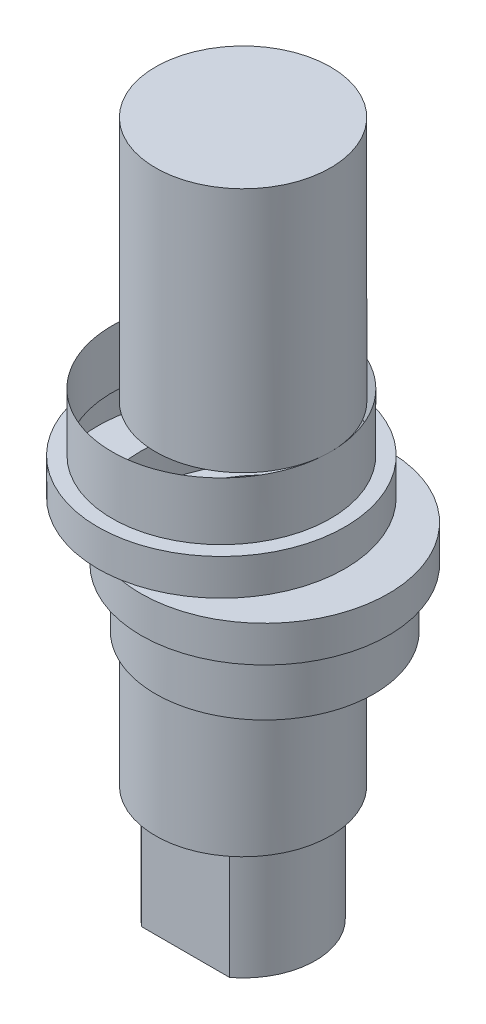
SolidWorks part; units mm, degrees
ref_plane "Front Plane" through (0, 0, 0) normal (0, 0, 1) x (1, 0, 0)
ref_plane "Top Plane" through (0, 0, 0) normal (0, 1, 0) x (1, 0, 0)
ref_plane "Right Plane" through (0, 0, 0) normal (1, 0, 0) x (0, 0, -1)
sketch "Sketch1" plane through (0, 0, 0) normal (0, 0, 1) x (1, 0, 0)
  line L0 (0, 0) -> (0, 40)
  line L1 (-1.5, 0) -> (-1.5, 40) construction
  line L2 (-1.5, 40) -> (1.5, 40) construction
  line L3 (-1.5, 0) -> (1.5, 0) construction
  line L4 (1.5, 0) -> (1.5, 40) construction
  line L6 (-6.05, 14) -> (9.05, 14)
  line L7 (-6.05, 14) -> (-6.05, 10)
  line L8 (-6.05, 10) -> (9.05, 10)
  line L9 (9.05, 14) -> (9.05, 10)
  line L10 (-6.05, 14) -> (9.05, 10) construction
  line L11 (-6.05, 10) -> (9.05, 14) construction
  line L12 (-9.05, 23) -> (6.05, 23)
  line L13 (-9.05, 23) -> (-9.05, 19)
  line L14 (-9.05, 19) -> (6.05, 19)
  line L15 (6.05, 23) -> (6.05, 19)
  line L16 (-9.05, 23) -> (6.05, 19) construction
  line L17 (-9.05, 19) -> (6.05, 23) construction
  line L20 (-6.05, 0) -> (6.05, 0)
  line L21 (-6.05, 0) -> (-6.05, 40)
  line L22 (-6.05, 40) -> (6.05, 40)
  line L23 (6.05, 0) -> (6.05, 40)
  line L24 (-6.05, 0) -> (6.05, 40) construction
  line L25 (-6.05, 40) -> (6.05, 0) construction
  point P7 (1.5, 12)
  point P12 (-1.5, 21)
  point P19 (0, 20)
  point P24 (0, 20)
  dimension "D1" = 3
  dimension "D2" = 40
  dimension "D3" = 15.1
  dimension "D4" = 4
  dimension "D5" = 5
  dimension "D6" = 12
revolve "Revolve4" add sketch "Sketch1" angle 360 about L0 region at (-3.025, 5, 0) region at (-3.025, 12, 0) region at (-3.025, 16.5, 0) region at (-3.025, 21, 0) region at (-3.025, 31.5, 0)
revolve "Revolve5" add sketch "Sketch1<5>" angle 360 about L1 region at (-7.55, 21, 0)
sketch "Sketch1<5>" plane through (0, 0, 0) normal (0, 0, 1) x (1, 0, 0) same geometry as "Sketch1"
revolve "Revolve6" add sketch "Sketch1<6>" angle 360 about L4 region at (7.55, 12, 0)
sketch "Sketch1<6>" plane through (0, 0, 0) normal (0, 0, 1) x (1, 0, 0) same geometry as "Sketch1"
sketch "Sketch2" plane through (0, 0, 0) normal (0, 0, 1) x (1, 0, 0)
  line L2 (0, 19) -> (0, 14) construction
  line L7 (-6.05, 19) -> (6.05, 19) construction
  line L10 (9.05, 14) -> (-6.05, 14) construction
  line L16 (-1.5, 19) -> (-1.5, 14) construction
  line L17 (1.5, 19) -> (1.5, 14) construction
  line L26 (-9.05, 19) -> (6.05, 19) construction
  line L27 (9.05, 14) -> (-6.05, 14) construction
  line L28 (-9.05, 19) -> (6.05, 19) construction
  line L29 (9.05, 10) -> (9.05, 14) construction
  line L30 (-1.5, 19) -> (-10.05, 19)
  line L31 (-1.5, 19) -> (-1.5, 16.5)
  line L32 (-1.5, 16.5) -> (-10.05, 16.5)
  line L33 (-10.05, 19) -> (-10.05, 16.5)
  line L34 (1.5, 16.5) -> (10.05, 16.5)
  line L35 (1.5, 16.5) -> (1.5, 14)
  line L36 (1.5, 14) -> (10.05, 14)
  line L37 (10.05, 16.5) -> (10.05, 14)
  dimension "D1" = 1
revolve "Revolve7" add sketch "Sketch2" angle 360 about L16 region at (-5.775, 17.75, 0)
revolve "Revolve8" add sketch "Sketch2<3>" angle 360 about L17 region at (5.775, 15.25, 0)
sketch "Sketch2<3>" plane through (0, 0, 0) normal (0, 0, 1) x (1, 0, 0) same geometry as "Sketch2"
sketch "Sketch3" plane through (0, 0, 0) normal (0, -1, 0) x (1, 0, 0)
  line L0 (-3.0412, 3.9688) -> (3.0412, 3.9688)
  line L1 (-3.0412, -3.9688) -> (3.0412, -3.9688)
  line L2 (0, -3.9688) -> (0, 0) construction
  line L3 (0, 0) -> (0, 3.9688) construction
  circle A0 centre (0, 0) radius 5
  dimension "D1" = 10
  dimension "D2" = 7.9375
extrude "Boss-Extrude1" add sketch "Sketch3" along normal blind 8 contours L1 A0 L0 region at (0, 0, 0)
sketch "Sketch4" plane through (0, -8, 0) normal (0, -1, 0) x (1, 0, 0)
  circle A0 centre (0, 0) radius 1.55
  dimension "D1" = 3.1
extrude "Cut-Extrude1" cut sketch "Sketch4" against normal up to surface (8 mm away) up to face at (0, 0, 0)
equation "\"Ratio\"= 15"
equation "\"Hull Diameter\"= 92"
equation "\"Fixed Ring Diameter\"= 76"
equation "\"Fixed Pin Diameter\"= 6"
equation "\"Output Ring Diameter\"= 40"
equation "\"Output Pin Diameter\"= 6"
equation "\"Disk Bearing Inner Diameter\"= 9"
equation "\"Disk Bearing Outer Diameter\"= 17"
equation "\"Disk Bearing Height\"= 5"
equation "\"Shaft Bearing Inner Diameter\"= 15"
equation "\"Shaft Bearing Outer Diameter\"= 21"
equation "\"Shaft Bearing Height\"= 4"
equation "\"Eccentricity\"= 1.5"
equation "\"Disk Height\"= 8"
equation "\"Disk Spacing\"= 5"
equation "\"Hull Height\"= 40"
equation "\"Shaft End Bearing Inner Diameter\"= 12"
equation "\"Shaft End Bearing Outer Diameter\"= 18"
equation "\"Shaft End Bearing Height\"= 4"
equation "\"Output Bearing Inner Diameter\"= 55"
equation "\"Output Bearing Outer Diameter\"= 72"
equation "\"Outer Bearing Height\"= 9"
equation "\"D1@Sketch1\"=\"Eccentricity\"*2"
equation "\"D2@Sketch1\"=\"Hull Height\""
equation "\"D3@Sketch1\"=\"Shaft Bearing Inner Diameter\"+0.1"
equation "\"D4@Sketch1\"=\"Shaft Bearing Height\""
equation "\"D5@Sketch1\"=\"Disk Spacing\""
